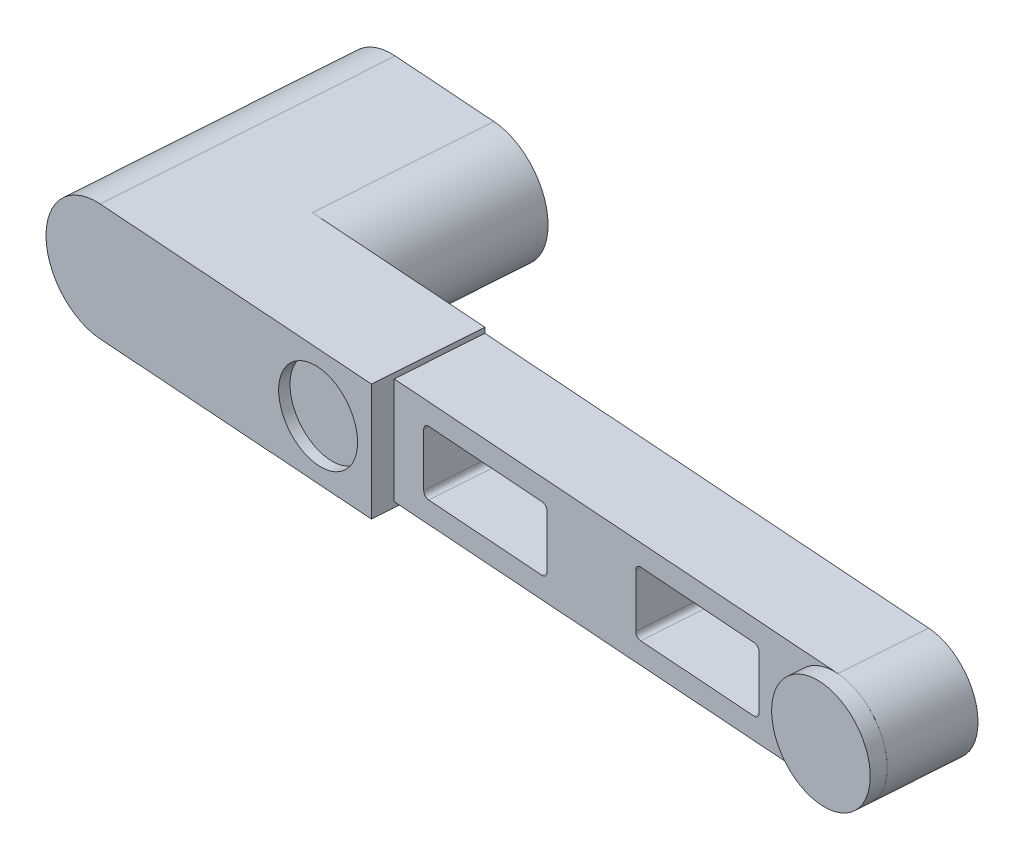
SolidWorks part; units mm, degrees
material "Cast Stainless Steel"
ref_plane "Front Plane" through (0, 0, 0) normal (0, 0, 1) x (1, 0, 0)
ref_plane "Top Plane" through (0, 0, 0) normal (0, 1, 0) x (1, 0, 0)
ref_plane "Right Plane" through (0, 0, 0) normal (1, 0, 0) x (0, 0, -1)
other "Center of Mass"
sketch "Sketch1" plane through (0, 0, 0) normal (1, 0, 0) x (0, 0, -1)
  line L0 (0, 0) -> (-500, 0) construction
  line L5 (-500, 50) -> (-50, 50)
  line L6 (50, -55) -> (-50, -55)
  line L7 (50, -55) -> (50, 55)
  line L8 (50, 55) -> (-50, 55)
  line L9 (-50, -55) -> (-50, 55)
  line L10 (50, -55) -> (-50, 55) construction
  line L11 (50, 55) -> (-50, -55) construction
  line L12 (-500, -50) -> (-50, -50)
  line L13 (0, 0) -> (280, 0)
  line L15 (280, 0) -> (50, 0)
  line L16 (280, 0) -> (280, 55)
  line L17 (280, 55) -> (50, 55)
  line L18 (50, 0) -> (50, 55)
  line L19 (280, 0) -> (50, 0)
  line L20 (280, 0) -> (280, -55)
  line L21 (280, -55) -> (50, -55)
  line L22 (50, 0) -> (50, -55)
  circle A0 centre (-500, 0) radius 50
  dimension "D1" = 100
  dimension "D2" = 110
  dimension "D3" = 100
  dimension "D4" = 500
  dimension "D5" = 280
extrude "Boss-Extrude1" add sketch "Sketch1" along normal blind 100 contours A0 L9 | A0 | L9 L6 L7 L8 | L21 L20 L13 L7 | L16 L17 L7 L13 region at (0, 0, 255.5167) region at (0, 0, 500) region at (0, 52.5, 48.5134) region at (0, 27.5, -165) region at (0, -27.5, -165)
sketch "Sketch2" plane through (0, 55, 0) normal (0, 1, 0) x (1, 0, 0)
  line L0 (0, 280) -> (260, 280)
  line L1 (260, 280) -> (260, 70)
  line L2 (260, 70) -> (100, 70)
  line L4 (0, 280) -> (0, -50)
  line L5 (0, -50) -> (100, -50)
  line L6 (100, -50) -> (100, 280)
  line L7 (100, 280) -> (0, 280)
  line L8 (0, 280) -> (0, -50)
  line L10 (100, -50) -> (100, 280)
  line L11 (100, 280) -> (0, 280)
  line L15 (0, -50) -> (100, -50)
  line M9 (100, -50) -> (100, 280)
  dimension "D2" = 260
  dimension "D3" = 210
  dimension "D1" = 0
extrude "Boss-Extrude2" add sketch "Sketch2" against normal up to surface (110 mm away) contours L2 L1 L0 M9 region at (180, 55, -175) up to face at (50, -55, -115)
sketch "Sketch3" plane through (260, 0, 0) normal (1, 0, 0) x (0, 0, -1)
  line L4 (70, -55) -> (280, -55)
  line L5 (280, -55) -> (280, 55)
  line L6 (280, 55) -> (70, 55)
  line L7 (70, 55) -> (70, -55)
  line L8 (70, -55) -> (280, -55)
  line L9 (280, -55) -> (280, 55)
  line L10 (280, 55) -> (70, 55)
  line L11 (70, 55) -> (70, -55)
  circle A0 centre (125, 0) radius 55
  circle A1 centre (225, 0) radius 55
  line M5 (70, -55) -> (280, -55)
  line M6 (280, -55) -> (280, 55)
  line M7 (280, 55) -> (70, 55)
  line M8 (70, 55) -> (70, -55)
  dimension "D1" = 0
extrude "Cut-Extrude1" cut sketch "Sketch3" against normal up to surface (260 mm away) contours A1 L9 M7 | A1 M5 M6 region at (260, -42.7148, -267.7148) region at (260, 42.7148, -267.7148) up to face at (0, 0, 86.25)
extrude "Cut-Extrude2" cut sketch "Sketch3<3>" against normal up to surface (160 mm away) contours A0 L10 M8 | A0 L11 M5 region at (260, -42.7148, -82.2852) region at (260, 42.7148, -82.2852) up to face at (100, 0, 138.75)
sketch "Sketch3<3>" plane through (260, 0, 0) normal (1, 0, 0) x (0, 0, -1) same geometry as "Sketch3"
ref_plane "Plane1" through (-27.37, 0, 0) normal (-1, 0, 0) x (0, 0, 1)
sketch "Sketch12" plane through (0, 0, 0) normal (-1, 0, 0) x (0, 0, 1)
  line L0 (500, 0) -> (-225, 0) construction
  line L1 (85, 30) -> (200, 30)
  line L2 (80, 25) -> (80, -25)
  line L3 (85, -30) -> (200, -30)
  line L4 (205, 25) -> (205, -25)
  line L5 (250, 30) -> (250, -35.6293) construction
  line L6 (-225, -55) -> (50, -55)
  line L7 (50, -55) -> (50, -50)
  line L8 (50, -50) -> (500, -50)
  line L9 (500, 50) -> (50, 50)
  line L10 (50, 50) -> (50, 55)
  line L11 (50, 55) -> (-225, 55)
  line L12 (-225, -55) -> (50, -55)
  line L13 (50, -55) -> (50, -50)
  line L14 (50, -50) -> (500, -50)
  line L15 (500, 50) -> (50, 50)
  line L16 (50, 50) -> (50, 55)
  line L17 (50, 55) -> (-225, 55)
  line L22 (415, -30) -> (300, -30)
  line L23 (420, 25) -> (420, -25)
  line L24 (295, 25) -> (295, -25)
  line L25 (415, 30) -> (300, 30)
  arc A0 (415, 30) -> (420, 25) centre (415, 25) cw
  arc A1 (415, -30) -> (420, -25) centre (415, -25) ccw
  arc A2 (-225, 55) -> (-225, -55) centre (-225, 0) ccw
  arc A3 (500, -50) -> (500, 50) centre (500, 0) ccw
  arc A4 (-225, 55) -> (-225, -55) centre (-225, 0) ccw
  arc A5 (500, -50) -> (500, 50) centre (500, 0) ccw
  arc A6 (295, 25) -> (300, 30) centre (300, 25) cw
  arc A7 (295, -25) -> (300, -30) centre (300, -25) ccw
  arc A8 (205, 25) -> (200, 30) centre (200, 25) ccw
  arc A9 (205, -25) -> (200, -30) centre (200, -25) cw
  arc A10 (85, 30) -> (80, 25) centre (85, 25) ccw
  arc A11 (80, -25) -> (85, -30) centre (85, -25) ccw
  point P22 (420, 30)
  point P25 (420, -30)
  point P28 (295, 30)
  point P31 (295, -30)
  point P36 (205, 30)
  point P39 (205, -30)
  point P42 (80, 30)
  point P45 (80, -30)
  dimension "D6" = 5
  dimension "D2" = 125
  dimension "D3" = 60
  dimension "D4" = 80
  dimension "D5" = 45
  dimension "D1" = 0
extrude "Cut-Extrude3" cut sketch "Sketch12" against normal up to surface (100 mm away) contours L4 L1 L2 L3 | L23 L25 L24 L22 region at (0, 0, 142.5) region at (0, 0, 357.5) up to face at (100, 0, 131.875)
sketch "Sketch13" plane through (100, 0, 0) normal (1, 0, 0) x (0, 0, -1)
  line L0 (-50, -48) -> (125, -48)
  line L1 (125, -48) -> (225, -48)
  line L2 (125, -55) -> (225, -55)
  line L3 (225, 55) -> (125, 55)
  line L4 (125, -55) -> (225, -55)
  line L5 (225, 55) -> (125, 55)
  line L6 (-50, -55) -> (125, -55)
  line L7 (125, 55) -> (-50, 55)
  line L8 (-50, 55) -> (-50, 50)
  line L9 (-50, 50) -> (-500, 50)
  line L10 (-500, -50) -> (-50, -50)
  line L11 (-50, -50) -> (-50, -55)
  line L12 (-50, -55) -> (125, -55)
  line L13 (125, 55) -> (-50, 55)
  line L14 (-50, 55) -> (-50, 50)
  line L15 (-50, 50) -> (-500, 50)
  line L16 (-500, -50) -> (-50, -50)
  line L17 (-50, -50) -> (-50, -55)
  line L18 (225, 48) -> (125, 48)
  line L19 (125, 48) -> (-50, 48)
  line L20 (-43, 55) -> (-43, 50)
  line L21 (-50, 43) -> (-500, 43)
  line L22 (-50, -55) -> (225, -55)
  line L23 (-50, -50) -> (-50, -55)
  line L24 (-500, -50) -> (-50, -50)
  line L25 (-50, 50) -> (-500, 50)
  line L26 (-50, 55) -> (-50, 50)
  line L27 (225, 55) -> (-50, 55)
  line L28 (-50, -55) -> (225, -55)
  line L29 (-50, -50) -> (-50, -55)
  line L30 (-500, -50) -> (-50, -50)
  line L31 (-50, 50) -> (-500, 50)
  line L32 (-50, 55) -> (-50, 50)
  line L33 (225, 55) -> (-50, 55)
  line L34 (-500, -43) -> (-50, -43)
  line L35 (-43, -50) -> (-43, -55)
  line L36 (-50, -48) -> (225, -48)
  line L37 (225, 48) -> (-50, 48)
  line L38 (-43, -50) -> (-43, -55)
  line L39 (-500, -43) -> (-50, -43)
  line L40 (-50, 43) -> (-500, 43)
  line L41 (-43, 55) -> (-43, 50)
  line L42 (-50, -48) -> (-50, -43)
  line L43 (-50, 43) -> (-50, 48)
  arc A0 (225, -48) -> (225, 48) centre (225, 0) ccw
  arc A1 (225, -48) -> (225, 48) centre (225, 0) ccw
  arc A2 (125, 55) -> (125, -55) centre (125, 0) ccw
  arc A3 (-500, 50) -> (-500, -50) centre (-500, 0) ccw
  arc A5 (-500, 50) -> (-500, -50) centre (-500, 0) ccw
  arc A6 (125, 55) -> (125, -55) centre (125, 0) ccw
  arc A7 (225, -55) -> (225, 55) centre (225, 0) ccw
  arc A8 (-500, 43) -> (-500, -43) centre (-500, 0) ccw
  arc A9 (225, -55) -> (225, 55) centre (225, 0) ccw
  arc A10 (225, -55) -> (225, 55) centre (225, 0) ccw
  arc A11 (-500, 50) -> (-500, -50) centre (-500, 0) ccw
  arc A12 (225, -55) -> (225, 55) centre (225, 0) ccw
  arc A13 (-500, 50) -> (-500, -50) centre (-500, 0) ccw
  arc A14 (-500, 43) -> (-500, -43) centre (-500, 0) ccw
  dimension "D1" = 0
  dimension "D2" = 0
  dimension "D3" = 0
  dimension "D4" = 7
move or copy body "Body-Move/Copy1" bodies to move or copy 113 copy no rotation origin (130, 0, 135) rotation axis (0, 1, 0) rotation angle 86
sketch "Sketch15" plane through (-17.83, 0, 254.9802) normal (-0.0698, 0, 0.9976) x (0.9976, 0, 0.0698)
  line L6 (-220.8995, -55) -> (54.1005, -55)
  line L7 (54.1005, -55) -> (54.1005, -50)
  line L8 (54.1005, -50) -> (504.1005, -50)
  line L9 (504.1005, 50) -> (54.1005, 50)
  line L10 (54.1005, 50) -> (54.1005, 55)
  line L11 (54.1005, 55) -> (-220.8995, 55)
  line L12 (-220.8995, -55) -> (54.1005, -55)
  line L13 (54.1005, -55) -> (54.1005, -50)
  line L14 (54.1005, -50) -> (504.1005, -50)
  line L15 (504.1005, 50) -> (54.1005, 50)
  line L16 (54.1005, 50) -> (54.1005, 55)
  line L17 (54.1005, 55) -> (-220.8995, 55)
  circle A0 centre (0, 0) radius 40
  arc A2 (-220.8995, 55) -> (-220.8995, -55) centre (-220.8995, 0) ccw
  arc A3 (504.1005, -50) -> (504.1005, 50) centre (504.1005, 0) ccw
  arc A4 (-220.8995, 55) -> (-220.8995, -55) centre (-220.8995, 0) ccw
  arc A5 (504.1005, -50) -> (504.1005, 50) centre (504.1005, 0) ccw
  point P0 (0, 0)
  dimension "D2" = 80
  dimension "D1" = 0
extrude "Cut-Extrude4" cut sketch "Sketch15" against normal blind 10 contours A0 region at (-17.83, 0, 254.9802)
sketch "Sketch16" plane through (-17.83, 0, 254.9802) normal (-0.0698, 0, 0.9976) x (0.9976, 0, 0.0698)
  point P0 (0, 0)
move or copy body "Body-Move/Copy2" bodies to move or copy 117 copy no translate (17.83, 0, -254.9802)
sketch "Sketch17" plane through (0, 0, 0) normal (-0.0698, 0, 0.9976) x (0.9976, 0, 0.0698)
  line L0 (54.1005, 50) -> (54.1005, -50)
  line L6 (-220.8995, -55) -> (54.1005, -55)
  line L7 (54.1005, -55) -> (54.1005, -50)
  line L8 (54.1005, -50) -> (504.1005, -50)
  line L9 (504.1005, 50) -> (54.1005, 50)
  line L10 (54.1005, 50) -> (54.1005, 55)
  line L11 (54.1005, 55) -> (-220.8995, 55)
  line L12 (-220.8995, -55) -> (54.1005, -55)
  line L13 (54.1005, -55) -> (54.1005, -50)
  line L14 (54.1005, -50) -> (504.1005, -50)
  line L15 (504.1005, 50) -> (54.1005, 50)
  line L16 (54.1005, 50) -> (54.1005, 55)
  line L17 (54.1005, 55) -> (-220.8995, 55)
  arc A2 (-220.8995, 55) -> (-220.8995, -55) centre (-220.8995, 0) ccw
  arc A3 (504.1005, -50) -> (504.1005, 50) centre (504.1005, 0) ccw
  arc A4 (-220.8995, 55) -> (-220.8995, -55) centre (-220.8995, 0) ccw
  arc A5 (504.1005, -50) -> (504.1005, 50) centre (504.1005, 0) ccw
  line M10 (204.1005, -30) -> (89.1005, -30)
  arc M11 (89.1005, -30) -> (84.1005, -25) centre (89.1005, -25) cw
  line M12 (84.1005, -25) -> (84.1005, 25)
  arc M13 (84.1005, 25) -> (89.1005, 30) centre (89.1005, 25) cw
  line M14 (89.1005, 30) -> (204.1005, 30)
  arc M15 (204.1005, 30) -> (209.1005, 25) centre (204.1005, 25) cw
  line M16 (209.1005, 25) -> (209.1005, -25)
  arc M17 (209.1005, -25) -> (204.1005, -30) centre (204.1005, -25) cw
  line M18 (419.1005, -30) -> (304.1005, -30)
  arc M19 (304.1005, -30) -> (299.1005, -25) centre (304.1005, -25) cw
  line M20 (299.1005, -25) -> (299.1005, 25)
  arc M21 (299.1005, 25) -> (304.1005, 30) centre (304.1005, 25) cw
  line M22 (304.1005, 30) -> (419.1005, 30)
  arc M23 (419.1005, 30) -> (424.1005, 25) centre (419.1005, 25) cw
  line M24 (424.1005, 25) -> (424.1005, -25)
  arc M25 (424.1005, -25) -> (419.1005, -30) centre (419.1005, -25) cw
  line M29 (54.1005, -50) -> (504.1005, -50)
  arc M30 (504.1005, -50) -> (504.1005, 50) centre (504.1005, 0) ccw
  line M31 (504.1005, 50) -> (54.1005, 50)
  dimension "D1" = 0
extrude "Cut-Extrude5" cut sketch "Sketch17" against normal blind 20 contours L0 M31 M29 M30 M25 M18 M19 M20 M21 M22 M23 M24 M17 M10 M11 M12 M13 M14 M15 M16 region at (278.4206, 44.901, 19.4691)
sketch "Sketch18" plane through (1.3951, 0, -19.9513) normal (-0.0698, 0, 0.9976) x (0.9976, 0, 0.0698)
  line L3 (504.1005, 50) -> (54.1005, 50)
  line L4 (54.1005, 50) -> (54.1005, -50)
  line L5 (54.1005, -50) -> (504.1005, -50)
  line L6 (504.1005, 50) -> (54.1005, 50)
  line L7 (54.1005, 50) -> (54.1005, -50)
  line L8 (54.1005, -50) -> (504.1005, -50)
  circle A0 centre (504.1005, 0) radius 50
  arc A1 (504.1005, -50) -> (504.1005, 50) centre (504.1005, 0) ccw
  arc A2 (504.1005, -50) -> (504.1005, 50) centre (504.1005, 0) ccw
  arc M24 (504.1005, -50) -> (504.1005, 50) centre (504.1005, 0) ccw
  dimension "D1" = 0
extrude "Boss-Extrude3" add sketch "Sketch18" along normal blind 15 separate body contours A0 M24 region at (504.2676, 0, 15.213)
